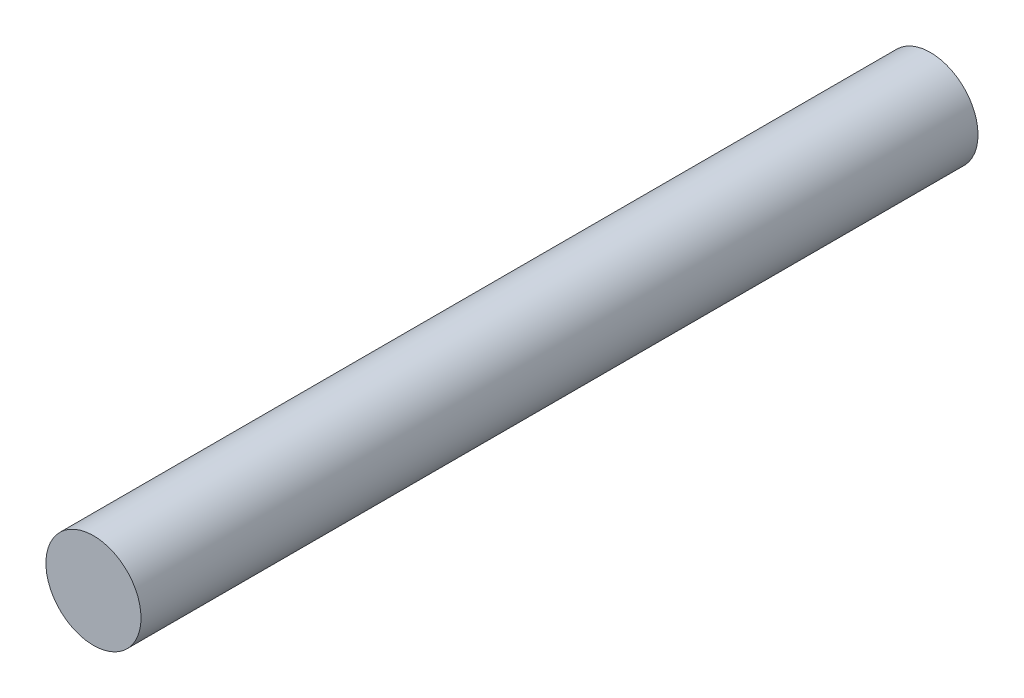
SolidWorks part; units mm, degrees
ref_plane "Front Plane" through (0, 0, 0) normal (0, 0, 1) x (1, 0, 0)
ref_plane "Top Plane" through (0, 0, 0) normal (0, 1, 0) x (1, 0, 0)
ref_plane "Right Plane" through (0, 0, 0) normal (1, 0, 0) x (0, 0, -1)
sketch "Sketch1" plane through (0, 0, 0) normal (0, 0, 1) x (1, 0, 0)
  circle A0 centre (0, 0) radius 2.5
  dimension "D1" = 5
extrude "Boss-Extrude1" add sketch "Sketch1" along normal blind 44
